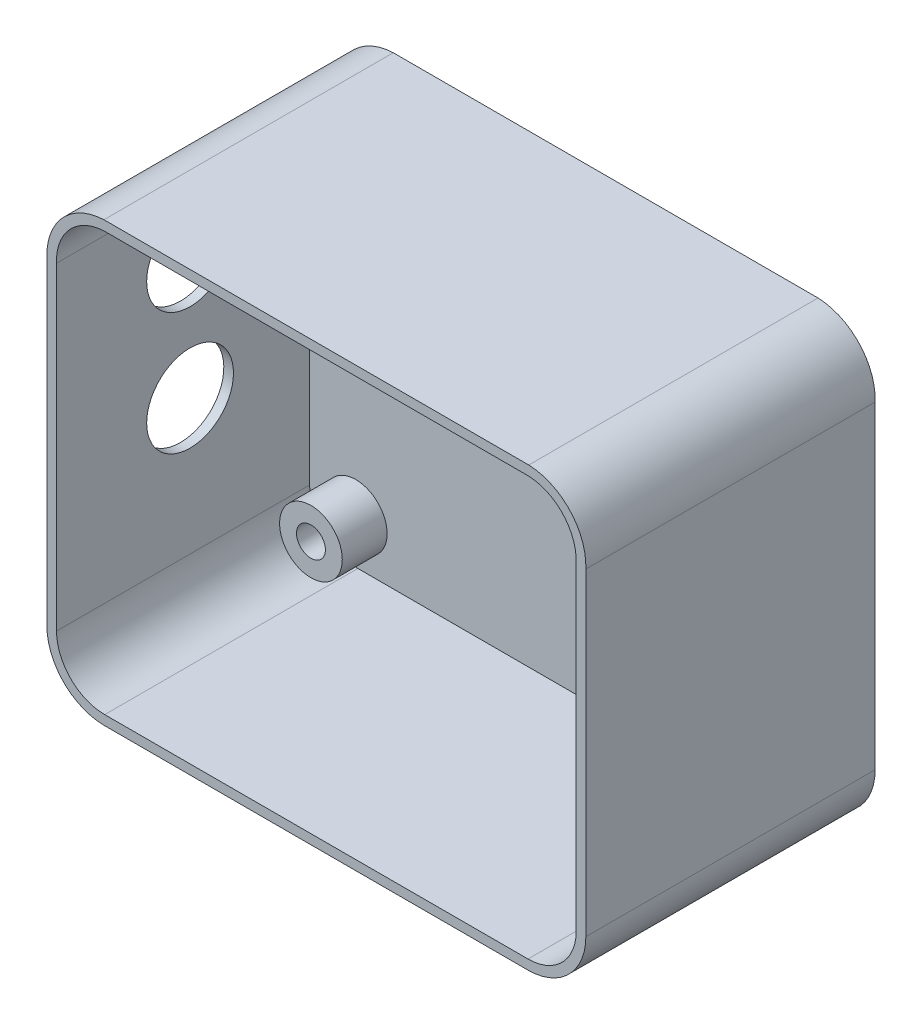
SolidWorks part; units mm, degrees
ref_plane "Front Plane" through (0, 0, 0) normal (0, 0, 1) x (1, 0, 0)
ref_plane "Top Plane" through (0, 0, 0) normal (0, 1, 0) x (1, 0, 0)
ref_plane "Right Plane" through (0, 0, 0) normal (1, 0, 0) x (0, 0, -1)
sketch "Sketch1" plane through (0, 0, 0) normal (0, 0, 1) x (1, 0, 0)
  line L0 (50.205, 38.4048) -> (6.31, 38.4048)
  line L1 (3.81, 35.6) -> (3.81, 2.5)
  line L2 (52.705, 35.6) -> (52.705, 2.5)
  line L3 (50.205, 0) -> (6.31, 0)
  line L4 (55.205, 35.54) -> (55.205, 2.5)
  line L5 (50.205, -2.5) -> (6.31, -2.5)
  line L6 (1.31, 35.54) -> (1.31, 2.5)
  line L7 (50.265, 40.9048) -> (6.25, 40.9048)
  line L8 (56.205, 35.5204) -> (56.205, 2.5)
  line L9 (50.205, -3.5) -> (6.31, -3.5)
  line L10 (0.31, 35.5204) -> (0.31, 2.5)
  line L11 (50.2847, 41.9048) -> (6.2303, 41.9048)
  arc A0 (6.31, 38.4048) -> (3.81, 35.6) centre (6.4624, 35.7524) ccw
  arc A1 (52.705, 35.6) -> (50.205, 38.4048) centre (50.0526, 35.7524) ccw
  arc A2 (50.205, 0) -> (52.705, 2.5) centre (50.205, 2.5) ccw
  arc A3 (3.81, 2.5) -> (6.31, 0) centre (6.31, 2.5) ccw
  circle A4 centre (6.096, 2.1336) radius 1.5
  circle A5 centre (50.5968, 2.1336) radius 1.5
  circle A6 centre (50.5968, 36.2712) radius 1.5
  circle A7 centre (6.096, 36.2712) radius 1.5
  arc A8 (50.205, -2.5) -> (55.205, 2.5) centre (50.205, 2.5) ccw
  arc A9 (1.31, 2.5) -> (6.31, -2.5) centre (6.31, 2.5) ccw
  arc A10 (6.25, 40.9048) -> (1.31, 35.54) centre (6.4624, 35.7524) ccw
  arc A11 (55.205, 35.54) -> (50.265, 40.9048) centre (50.0526, 35.7524) ccw
  arc A12 (50.205, -3.5) -> (56.205, 2.5) centre (50.205, 2.5) ccw
  arc A13 (0.31, 2.5) -> (6.31, -3.5) centre (6.31, 2.5) ccw
  arc A14 (6.2303, 41.9048) -> (0.31, 35.5204) centre (6.4624, 35.7524) ccw
  arc A15 (56.205, 35.5204) -> (50.2847, 41.9048) centre (50.0526, 35.7524) ccw
  dimension "D1" = 2.5
  dimension "D2" = 1
extrude "Boss-Extrude2" add sketch "Sketch1" along normal blind 3.75 contours L4 A11 L7 A10 L6 A9 L5 A8 A3 L1 A0 L0 A1 L2 A2 L3 | L1 A3 L3 A2 L2 A1 L0 A0 A7 A6 A5 A4 region at (28.2561, 19.1994, 0) region at (54.5129, 19.02, 0)
extrude "Boss-Extrude3" add sketch "Sketch1<3>" along normal blind 30 contours L8 A15 L11 A14 L10 A13 L9 A12 A11 L4 A8 L5 A9 L6 A10 L7 region at (55.4848, 19.0102, 0)
sketch "Sketch1<3>" plane through (0, 0, 0) normal (0, 0, 1) x (1, 0, 0) same geometry as "Sketch1"
sketch "Sketch2" plane through (0, 0, 0) normal (0, 0, -1) x (-1, 0, 0)
  line L1 (-50.5968, 5.3668) -> (-53.3968, 3.7502)
  line L2 (-53.3968, 3.7502) -> (-53.3968, 0.517)
  line L3 (-53.3968, 0.517) -> (-50.5968, -1.0996)
  line L4 (-50.5968, -1.0996) -> (-47.7968, 0.517)
  line L5 (-47.7968, 0.517) -> (-47.7968, 3.7502)
  line L6 (-47.7968, 3.7502) -> (-50.5968, 5.3668)
  line L7 (-47.7968, 37.8878) -> (-50.5968, 39.5044)
  line L8 (-50.5968, 39.5044) -> (-53.3968, 37.8878)
  line L9 (-53.3968, 37.8878) -> (-53.3968, 34.6546)
  line L10 (-53.3968, 34.6546) -> (-50.5968, 33.038)
  line L11 (-50.5968, 33.038) -> (-47.7968, 34.6546)
  line L12 (-47.7968, 34.6546) -> (-47.7968, 37.8878)
  line L13 (-6.096, 39.5044) -> (-8.896, 37.8878)
  line L14 (-8.896, 37.8878) -> (-8.896, 34.6546)
  line L15 (-8.896, 34.6546) -> (-6.096, 33.038)
  line L16 (-6.096, 33.038) -> (-3.296, 34.6546)
  line L17 (-3.296, 34.6546) -> (-3.296, 37.8878)
  line L18 (-3.296, 37.8878) -> (-6.096, 39.5044)
  line L19 (-6.096, 5.3668) -> (-8.896, 3.7502)
  line L20 (-8.896, 3.7502) -> (-8.896, 0.517)
  line L21 (-8.896, 0.517) -> (-6.096, -1.0996)
  line L22 (-6.096, -1.0996) -> (-3.296, 0.517)
  line L23 (-3.296, 0.517) -> (-3.296, 3.7502)
  line L24 (-3.296, 3.7502) -> (-6.096, 5.3668)
  circle A0 centre (-50.5968, 2.1336) radius 2.8 construction
  circle A1 centre (-50.5968, 36.2712) radius 2.8 construction
  circle A2 centre (-6.096, 36.2712) radius 2.8 construction
  circle A3 centre (-6.096, 2.1336) radius 2.8 construction
  dimension "D1" = 5.6
  dimension "D2" = 5.6
  dimension "D3" = 5.6
  dimension "D4" = 5.6
extrude "Cut-Extrude1" cut sketch "Sketch2" against normal blind 2.4
sketch "Sketch3" plane through (0, 0, 3.75) normal (0, 0, 1) x (1, 0, 0)
  circle A0 centre (6.096, 36.2712) radius 1.5 construction
  circle A1 centre (6.096, 2.1336) radius 1.5 construction
  circle A2 centre (50.5968, 36.2712) radius 1.5 construction
  circle A3 centre (50.5968, 2.1336) radius 1.5 construction
  circle A4 centre (6.096, 36.2712) radius 1.5
  circle A5 centre (6.096, 2.1336) radius 1.5
  circle A6 centre (50.5968, 36.2712) radius 1.5
  circle A7 centre (50.5968, 2.1336) radius 1.5
  circle A8 centre (6.096, 36.2712) radius 3.25
  circle A9 centre (6.096, 2.1336) radius 3.25
  circle A10 centre (50.5968, 2.1336) radius 3.25
  circle A11 centre (50.5968, 36.2712) radius 3.25
  dimension "D1" = 1.75
extrude "Boss-Extrude4" add sketch "Sketch3" along normal blind 4.65
sketch "Sketch4" plane through (0.31, 0, 0) normal (-1, 0, 0) x (0, 0, 1)
  circle A0 centre (16.15, 29.21) radius 4.5
  circle A1 centre (16.15, 16.51) radius 4.5
  dimension "D1" = 9
  dimension "D2" = 9
extrude "Cut-Extrude2" cut sketch "Sketch4" against normal up to surface (1 mm away) up to face at (1.31, 19.02, 16.875)
